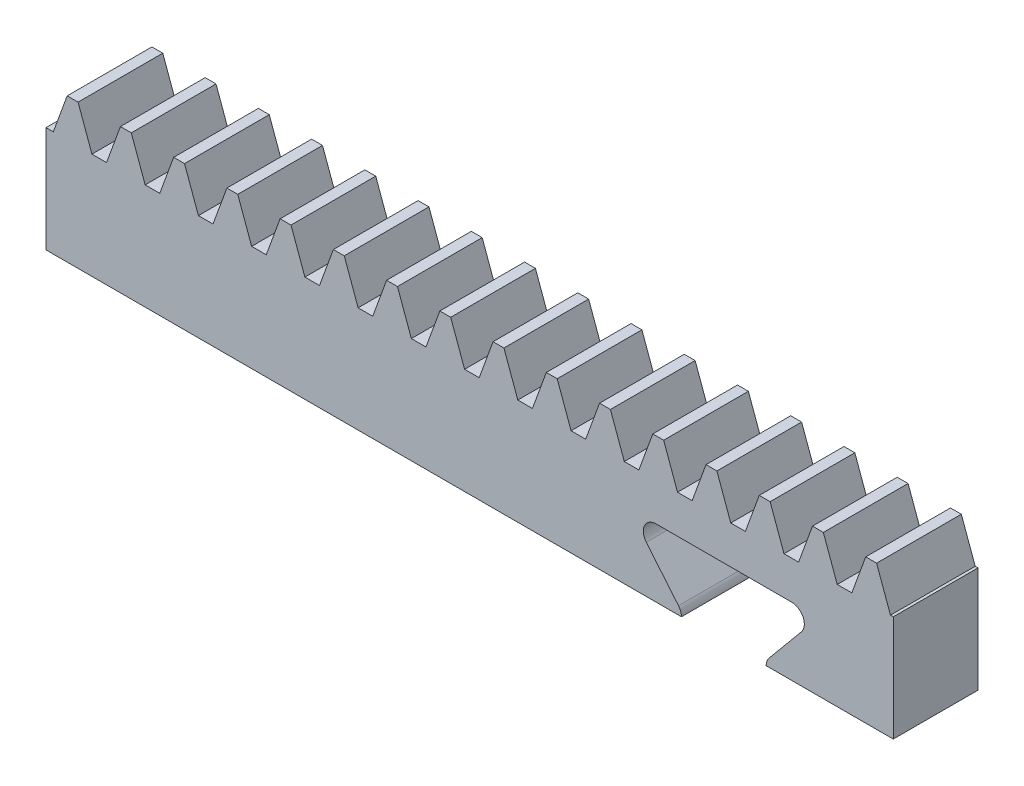
SolidWorks part; units mm, degrees
extrude "Blank" add sketch "BlankSke" against normal blind 10
sketch "BlankSke" plane through (0, 0, 0) normal (0, 0, 1) x (1, 0, 0)
  line L1 (0, 0) -> (100, 0)
  line L2 (0, 0) -> (0, 17)
  line L3 (0, 17) -> (100, 17)
  line L4 (100, 0) -> (100, 17)
  dimension "Length" = 100
ref_plane "Plane1" through (0, 0, 0) normal (0, 0, 1) x (1, 0, 0)
ref_plane "Plane2" through (0, 0, 0) normal (0, 1, 0) x (1, 0, 0)
ref_plane "Plane3" through (0, 0, 0) normal (1, 0, 0) x (0, 0, -1)
other "Configuration Table"
sketch "HoldingSke" plane through (0, 0, 0) normal (0, 1, 0) x (1, 0, 0)
  line L0 (0, 0) -> (0.0696, 0.4951)
  line L1 (-15, 0) -> (100, 0) construction
  line L2 (0, 0) -> (-2.1039, 2.3779)
  line L3 (0, 0) -> (-11.863, 4.5341)
  line L4 (0, 0) -> (8.2587, 2.5249)
  line L5 (0, 0) -> (-23.7986, -8.8762)
  line L6 (0, 0) -> (-10.5278, -7.1032)
  line L9 (-71.009, 38.7566) -> (22.9603, 72.9586)
  line L10 (-76.2, 4.3779) -> (-61.2, 4.3779)
  line L11 (0, 0) -> (-10, 0)
  line L12 (-76.2, 101.6) -> (-76.133, 101.6)
  line L13 (24.9733, 27.94) -> (52.9518, 28.4284)
  line L14 (24.9733, 27.94) -> (24.9743, 27.94)
  line L15 (24.9733, 27.94) -> (100.4006, 29.5858)
  circle A0 centre (0, 0) radius 19.05
  circle A1 centre (0, 0) radius 7.5
  circle A2 centre (0, 0) radius 12.7
  dimension "Num_teeth" = 17
  dimension "Width" = 10
  dimension "Length" = 100
  dimension "Pitch_height" = 15
sketch "TooCutSkeIll" plane through (0, 0, 0) normal (0, 0, 1) x (1, 0, 0)
  line L0 (-2.4806, 16.9474) -> (-0.9819, 12.8296)
  line L1 (-0.5111, 12.5) -> (0.5111, 12.5)
  line L2 (0.9819, 12.8296) -> (2.4806, 16.9474)
  line L3 (100, 17) -> (0, 17) construction
  line L4 (0, 0) -> (0, 64.897) construction
  line L5 (-13.208, 15) -> (12.954, 15) construction
  line L6 (0, 0) -> (100, 0) construction
  line L7 (1.7718, 15) -> (1.7718, 48.7463) construction
  line L8 (-1.7718, 15) -> (-1.7718, 48.7463) construction
  line L9 (2.5558, 17) -> (2.5558, 17.0254)
  line L10 (-2.5558, 17) -> (-2.5558, 17.0254)
  line L11 (-2.5558, 17.0254) -> (2.5558, 17.0254)
  arc A0 (0.5111, 12.5) -> (0.9819, 12.8296) centre (0.5111, 13.001) ccw
  arc A1 (-0.9819, 12.8296) -> (-0.5111, 12.5) centre (-0.5111, 13.001) ccw
  arc A2 (2.5558, 17) -> (2.4806, 16.9474) centre (2.5558, 16.92) ccw
  arc A3 (-2.4806, 16.9474) -> (-2.5558, 17) centre (-2.5558, 16.92) ccw
  dimension "Addendum_plus" = 2.0254
  dimension "Pitch_height" = 15
  dimension "Pressure_angle" = 20
  dimension "Gap_width" = 3.5436
  dimension "Dedendum" = 2.5
extrude "ToothCutIll" [suppressed] cut sketch "TooCutSkeIll" against normal through all
sketch "TooCutSkeSim" plane through (0, 0, 0) normal (0, 0, 1) x (1, 0, 0)
  line L0 (0.8619, 12.5) -> (-0.8619, 12.5)
  line L1 (2.509, 17.0254) -> (0.8619, 12.5)
  line L2 (0, 17.4625) -> (0, 53.467) construction
  line L3 (2.509, 17.0254) -> (-2.509, 17.0254)
  line L6 (-2.509, 17.0254) -> (-0.8619, 12.5)
  line L9 (-1.7718, 15) -> (1.7718, 15) construction
  line L10 (0, 0) -> (100, 0) construction
  line L11 (1.7718, 15) -> (1.7718, 53.467) construction
  line L12 (-1.7718, 15) -> (-1.7718, 53.467) construction
  dimension "Addendum_plus" = 2.0254
  dimension "Pitch_height" = 15
  dimension "Pressure_angle" = 20
  dimension "Gap_width" = 3.5436
  dimension "Dedendum" = 2.5
extrude "ToothCutSim" cut sketch "TooCutSkeSim" against normal through all
pattern_linear "TeethCuts" count 17 spacing 6.2832 along (1, 0, 0) of "ToothCutIll", "ToothCutSim"
sketch "Sketch1" plane through (0, 0, 0) normal (0, 0, 1) x (1, 0, 0)
  line L0 (80, 0) -> (80, 10.8168) construction
  line L1 (0, 0) -> (100, 0) construction
  line L3 (88, 8) -> (72, 8)
  line L4 (70.8462, 5.5414) -> (74.6538, 0.9586)
  line L5 (89.1538, 5.5414) -> (85.3462, 0.9586)
  line L6 (85, 0) -> (75, 0)
  line L7 (100, 0) -> (100, 12.5) construction
  arc A0 (72, 8) -> (70.8462, 5.5414) centre (72, 6.5) ccw
  arc A1 (88, 8) -> (89.1538, 5.5414) centre (88, 6.5) cw
  arc A2 (75, 0) -> (74.6538, 0.9586) centre (73.5, 0) ccw
  arc A3 (85, 0) -> (85.3462, 0.9586) centre (86.5, 0) cw
  point P9 (80, 8)
  point P24 (80, 0)
  dimension "D2" = 3
  dimension "D3" = 3
  dimension "D1" = 20
  dimension "D4" = 16
  dimension "D5" = 10
  dimension "D6" = 8
extrude "Cut-Extrude1" cut sketch "Sketch1" against normal through all
equation "' \"Module@HoldingSke\" = 6.35"
equation "' \"Num_teeth@HoldingSke\" = 12"
equation "' \"Ap@HoldingSke\" =  20"
equation "' \"Ap@HoldingSke\" = 20"
equation "' \"Width@HoldingSke\" = 0.25 * 25.4"
equation "' \"Show_teeth@HoldingSke\" = 500"
equation "' \"Backlash@HoldingSke\" = 0.009 * 25.4"
equation "' \"Addendum_fac@HoldingSke\" = 1.0"
equation "' \"Dedendum_fac@HoldingSke\" = 1.25"
equation "' \"Dedendum_add@HoldingSke\" = 0.00005 * 25.4"
equation "' \"Clearance_fac@HoldingSke\" = 0.25"
equation "' \"Pitch_height@HoldingSke\" = 1 * 25.4"
equation "' \"Length@HoldingSke\" = 4.71 * 25.4"
equation "\"Pitch@HoldingSke\" = 1 / \"Module@HoldingSke\""
equation "\"MPH@HoldingSke\" = \"Dedendum_fac@HoldingSke\" / \"Pitch@HoldingSke\" + 2 * \"Dedendum_add@HoldingSke\" + 0.002 * 25.4"
equation "\"MPH@HoldingSke\" = ((sgn( \"MPH@HoldingSke\" - \"Pitch_height@HoldingSke\")+1)*( \"MPH@HoldingSke\" - \"Pitch_height@HoldingSke\"))/2 + \"Pitch_height@HoldingSke\""
equation "\"Blank_height@BlankSke\" = \"Pitch_height@HoldingSke\" + \"Addendum_fac@HoldingSke\"  / \"Pitch@HoldingSke\" "
equation "\"Length@BlankSke\" =  \"Length@HoldingSke\""
equation "\"Face_width@Blank\" = \"Width@HoldingSke\""
equation "\"Pressure_angle@TooCutSkeIll\" = \"Ap@HoldingSke\""
equation "\"Addendum_plus@TooCutSkeIll\" =  \"Addendum_fac@HoldingSke\"  / \"Pitch@HoldingSke\" + 0.001 *25.4"
equation "\"Dedendum@TooCutSkeIll\" = \"Dedendum_fac@HoldingSke\"  / \"Pitch@HoldingSke\""
equation "\"Pitch_height@TooCutSkeIll\" =  \"MPH@HoldingSke\""
equation "\"Gap_width@TooCutSkeIll\" = 3.14159265 / 2 / \"Pitch@HoldingSke\" + 6 * \"Backlash@HoldingSke\""
equation "\"Pressure_angle@TooCutSkeSim\" = \"Ap@HoldingSke\""
equation "\"Addendum_plus@TooCutSkeSim\" =  \"Addendum_fac@HoldingSke\"  / \"Pitch@HoldingSke\" + 0.001 * 25.4"
equation "\"Dedendum@TooCutSkeSim\" = \"Dedendum_fac@HoldingSke\"  / \"Pitch@HoldingSke\""
equation "\"Pitch_height@TooCutSkeSim\" =  \"MPH@HoldingSke\""
equation "\"Gap_width@TooCutSkeSim\" = 3.14159265 / 2 / \"Pitch@HoldingSke\" + 6 * \"Backlash@HoldingSke\""
equation "\"Root_fillet@TooCutSkeIll\" = \"Clearance_fac@HoldingSke\" / \"Pitch@HoldingSke\" + \"Dedendum_add@HoldingSke\""
equation "\"Break_rad@TooCutSkeIll\" = 0.02 / \"Pitch@HoldingSke\" * 2"
equation "\"Linear_pitch@TeethCuts\" = 3.14159265 / \"Pitch@HoldingSke\""
equation "\"Num_teeth@HoldingSke\" = int( ( \"Length@HoldingSke\" + 0 ) / (3.14159265 / \"Pitch@HoldingSke\")) + 0.9999  + 1"
equation " \"Num_teeth@TeethCuts\" = int( \"Show_teeth@HoldingSke\" ) + 1"
equation " \"Num_teeth@TeethCuts\" = ((sgn( \"Num_teeth@TeethCuts\" - \"Num_teeth@HoldingSke\" )-1)*( \"Num_teeth@TeethCuts\" - \"Num_teeth@HoldingSke\" ))/-2+ \"Num_teeth@HoldingSke\""
equation " \"Num_teeth@TeethCuts\" = ((sgn( \"Num_teeth@TeethCuts\" - 2.0)+1)*( \"Num_teeth@TeethCuts\" - 2.0))/2 +2.0"
